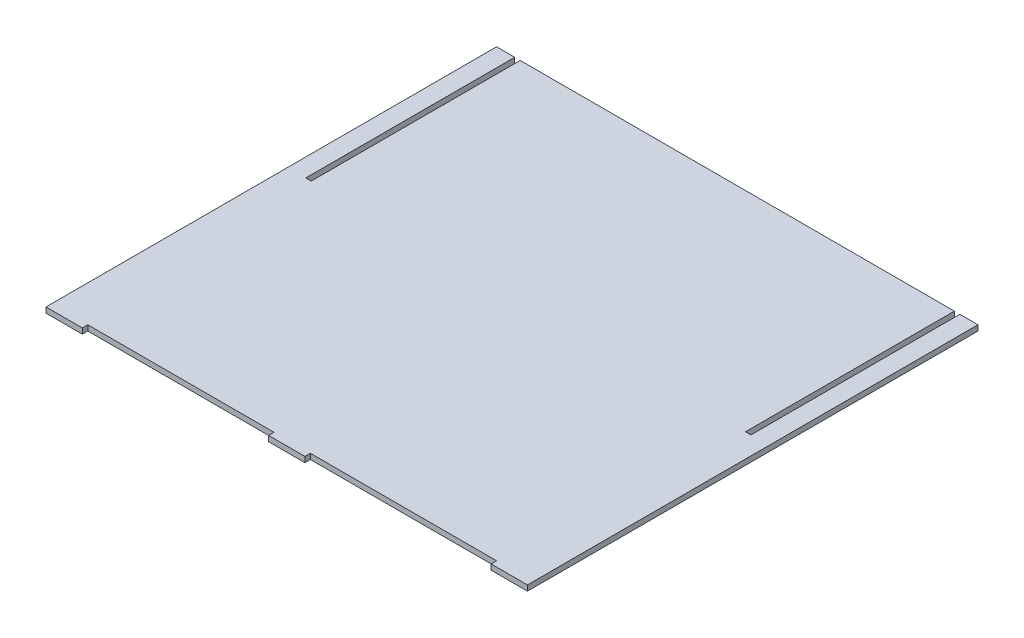
SolidWorks part; units mm, degrees
ref_plane "Front Plane" through (0, 0, 0) normal (0, 0, 1) x (1, 0, 0)
ref_plane "Top Plane" through (0, 0, 0) normal (0, 1, 0) x (1, 0, 0)
ref_plane "Right Plane" through (0, 0, 0) normal (1, 0, 0) x (0, 0, -1)
sketch "Sketch1" plane through (0, 0, 0) normal (0, 1, 0) x (1, 0, 0)
  line L0 (-530, 0) -> (-490, 0)
  line L2 (0, 0) -> (0, 496)
  line L3 (0, 496) -> (-530, 496)
  line L4 (-530, 0) -> (-530, 496)
  line L5 (-490, 0) -> (-490, 6)
  line L6 (0, 0) -> (-40, 0)
  line L7 (-40, 0) -> (-40, 6)
  line L8 (-40, 6) -> (-245, 6)
  line L9 (-245, 6) -> (-245, 0)
  line L10 (-245, 0) -> (-285, 0)
  line L11 (-285, 0) -> (-285, 6)
  line L12 (-285, 6) -> (-490, 6)
  dimension "D1" = 530
  dimension "D2" = 496
  dimension "D3" = 40
  dimension "D4" = 6
extrude "Boss-Extrude1" add sketch "Sketch1" along normal blind 6 contours L4 L3 L2 L6 L7 L8 L9 L10 L11 L12 L5 L0
sketch "Sketch2" plane through (0, 6, 0) normal (0, 1, 0) x (1, 0, 0)
  line L1 (-20, 496) -> (-26, 496)
  line L2 (-20, 496) -> (-20, 266)
  line L3 (-20, 266) -> (-26, 266)
  line L4 (-26, 496) -> (-26, 266)
  line L6 (0, 0) -> (0, 496) construction
  line L7 (0, 496) -> (-530, 496) construction
  dimension "D1" = 6
  dimension "D2" = 20
  dimension "D3" = 230
extrude "Cut-Extrude1" cut sketch "Sketch2" against normal blind 6
pattern_linear "LPattern1" count 2 spacing 484 along (-1, 0, 0) of "Cut-Extrude1"
